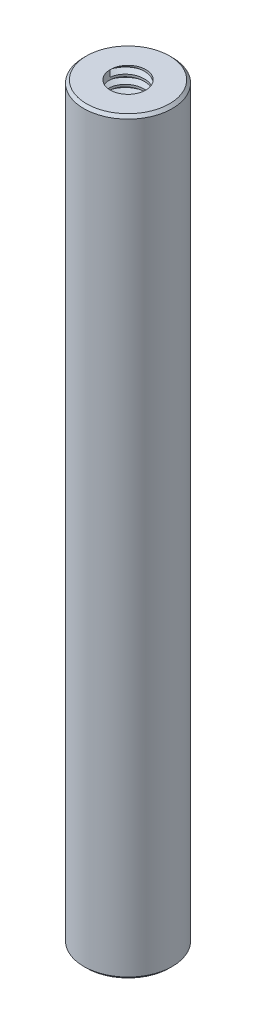
SolidWorks part; units mm, degrees
material "6061-T6 (SS)"
ref_plane "Alzado" through (0, 0, 0) normal (0, 0, 1) x (1, 0, 0)
ref_plane "Planta" through (0, 0, 0) normal (0, 1, 0) x (1, 0, 0)
ref_plane "Vista lateral" through (0, 0, 0) normal (1, 0, 0) x (0, 0, -1)
sketch "Croquis2" plane through (0, 0, 0) normal (0, 1, 0) x (1, 0, 0)
  circle A0 centre (0, 0) radius 6.35
  dimension "D1" = 12.7
extrude "Saliente-Extruir1" add sketch "Croquis2" along normal mid plane 107.3813
chamfer "Chaflán1" distance 0.3969 angle 45 2 edges at (0, -53.6907, 6.35) (0, 53.6907, 6.35)
sketch "Croquis3" plane through (0, 0, 0) normal (0, 1, 0) x (1, 0, 0)
  circle A0 centre (0, 0) radius 2.5527
  dimension "D1" = 5.1054
extrude "Tap Hole 1" cut sketch "Croquis3" against normal blind 19.05 from surface starting at face at (0, 53.6907, 5.9531)
extrude "Tap Hole 2" cut sketch "Croquis3<2>" along normal blind 19.05 from surface starting at face at (0, -53.6907, 5.9531)
sketch "Croquis3<2>" plane through (0, 0, 0) normal (0, 1, 0) x (1, 0, 0) same geometry as "Croquis3"
sketch "Croquis4" plane through (0, 0, 0) normal (0, 1, 0) x (1, 0, 0)
  circle A0 centre (0, 0) radius 3.2639
  dimension "D1" = 6.5278
extrude "Clearance Hole" [suppressed] cut sketch "Croquis4" against normal through all both and the other way through all
thread "Rosca1" pitch 1.27 method cut profile "Perfil de rosca1" start angle 0, offset 0, length 0, pitch 1.27, diameter 5.1054
ref_plane "Plano1" through (-2.5527, 53.6907, 0) normal (0, 0, 1) x (-1, 0, 0)
sketch "Perfil de rosca1" plane through (-2.5527, 53.6907, 0) normal (0, 0, 1) x (-1, 0, 0)
  line L0 (0, 0) -> (0, 1.27) construction
  line L1 (0, 0) -> (0.6874, 0.3969)
  line L2 (0.6874, 0.3969) -> (0.6874, 0.5556)
  line L3 (0.6874, 0.5556) -> (0, 0.9525)
  line L4 (0.6874, 0.4762) -> (0, 0.4762) construction
  line L11 (0, 0) -> (0, 0.9525)
  point P2 (0, 0)
  dimension "Pitch" = 1.27
  dimension "Profile_Angle" = 60
  dimension "Profile_Land" = 0.1588
  dimension "Profile_Height" = 0.6874
thread "Rosca2" pitch 1.27 method cut profile "Perfil de rosca2" start angle 0, offset 0, length 0, pitch 1.27, diameter 5.1054
ref_plane "Plano2" through (2.5527, -53.6907, 0) normal (0, 0, 1) x (1, 0, 0)
sketch "Perfil de rosca2" plane through (2.5527, -53.6907, 0) normal (0, 0, 1) x (1, 0, 0)
  line L0 (0, 0) -> (0, 1.27) construction
  line L1 (0, 0) -> (0.6874, 0.3969)
  line L2 (0.6874, 0.3969) -> (0.6874, 0.5556)
  line L3 (0.6874, 0.5556) -> (0, 0.9525)
  line L4 (0.6874, 0.4762) -> (0, 0.4762) construction
  line L11 (0, 0) -> (0, 0.9525)
  point P2 (0, 0)
  dimension "Pitch" = 1.27
  dimension "Profile_Angle" = 60
  dimension "Profile_Land" = 0.1588
  dimension "Profile_Height" = 0.6874
equation "\"OD\"= 0.5pulgadas"
equation "\"Largo\"= 2.11380512 * 2pulgadas"
equation "\"Tap Hole\"= IIF ( \"OD\" = 0.375pulgadas , 0.1590pulgadas , 0.201pulgadas )"
equation "\"Spacer Hole\"= IIF ( \"OD\" = 0.375pulgadas , 0.196pulgadas , 0.257pulgadas )"
equation "\"D1@Croquis2\"=\"OD\""
equation "\"D1@Saliente-Extruir1\"=\"Largo\""
equation "\"D1@Croquis3\"=\"Tap Hole\""
equation "\"D1@Croquis4\"=\"Spacer Hole\""
